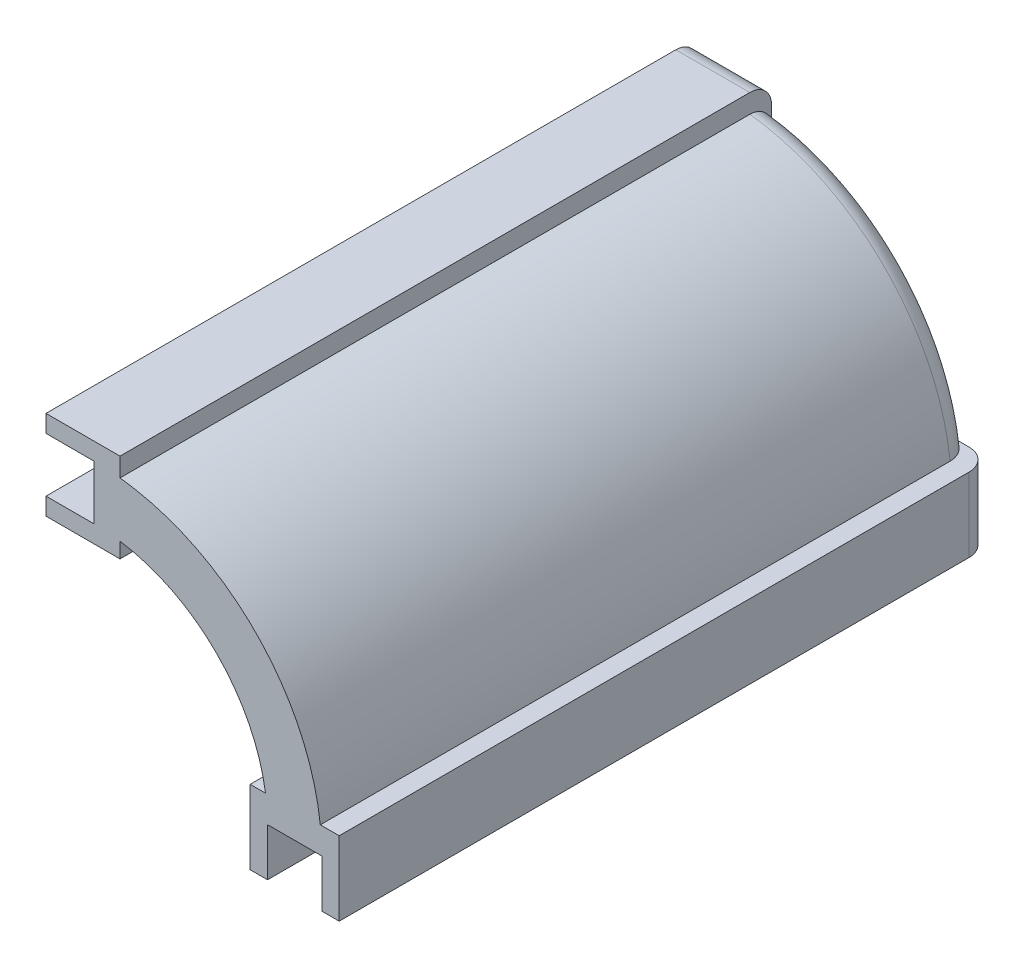
SolidWorks part; units mm, degrees
ref_plane "前视基准面" through (0, 0, 0) normal (0, 0, 1) x (1, 0, 0)
ref_plane "上视基准面" through (0, 0, 0) normal (0, 1, 0) x (1, 0, 0)
ref_plane "右视基准面" through (0, 0, 0) normal (1, 0, 0) x (0, 0, -1)
sketch "草图1" plane through (0, 0, 0) normal (0, 0, 1) x (1, 0, 0)
  line L0 (0, 40) -> (0, 52.5)
  line L1 (40, 0) -> (52.5, 0)
  arc A0 (40, 0) -> (0, 40) centre (0, 0) ccw
  arc A1 (52.5, 0) -> (0, 52.5) centre (0, 0) ccw
extrude "凸台-拉伸1" add sketch "草图1" along normal blind 150
sketch "草图2" plane through (0, 0, 0) normal (0, 0, -1) x (-1, 0, 0)
  line L1 (11, 52.5) -> (11, 56.5)
  line L2 (-52.5, -11) -> (-52.5, 0)
  line L3 (-52.5, 0) -> (-40, 0)
  line L4 (-40, 0) -> (-40, -11)
  line L5 (-40, -11) -> (-36, -11)
  line L6 (11, 56.5) -> (-6.041, 56.5)
  line L7 (-6.041, 56.5) -> (-6.041, 36)
  line L8 (-36, 6.041) -> (-36, -11)
  line L9 (-56.5, 6.041) -> (-36, 6.041)
  line L10 (-56.5, -11) -> (-56.5, 6.041)
  line L11 (-6.041, 36) -> (11, 36)
  line L12 (11, 40) -> (11, 36)
  line L13 (0, 40) -> (11, 40)
  line L14 (0, 52.5) -> (0, 40)
  line L15 (11, 52.5) -> (0, 52.5)
  line L16 (-52.5, -11) -> (-56.5, -11)
extrude "凸台-拉伸2" add sketch "草图2" against normal blind 150
fillet "圆角1" radius 5 1 edges at (37.1231, 37.1231, 0)
fillet "圆角2" radius 5 1 edges at (28.2843, 28.2843, 0)
fillet "圆角3" radius 5 1 edges at (-2.4795, 56.5, 0)
fillet "圆角4" radius 5 2 edges at (56.5, -2.4795, 0) (-2.4795, 36, 0)
fillet "圆角5" radius 5 1 edges at (36, -2.4795, 0)
